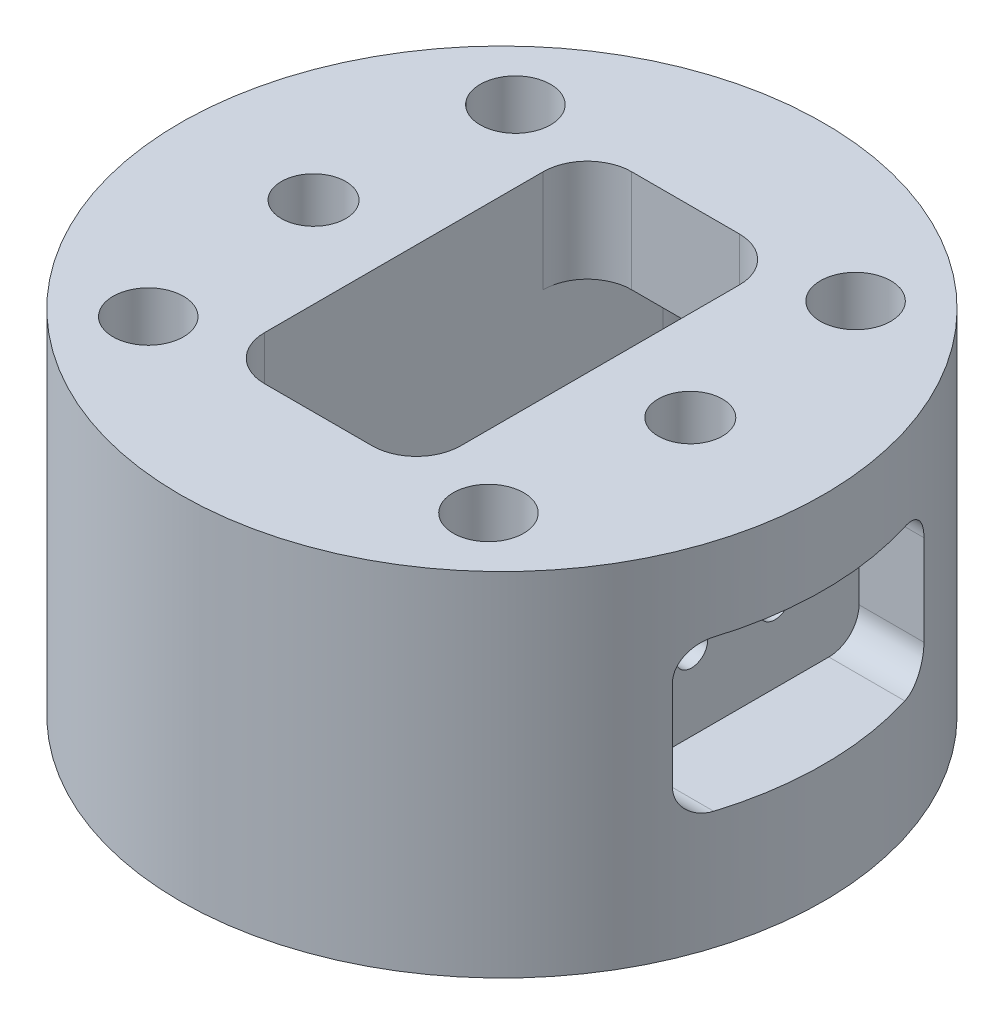
SolidWorks part; units mm, degrees
material "6061 Alloy"
ref_plane "Front Plane" through (0, 0, 0) normal (0, 0, 1) x (1, 0, 0)
ref_plane "Top Plane" through (0, 0, 0) normal (0, 1, 0) x (1, 0, 0)
ref_plane "Right Plane" through (0, 0, 0) normal (1, 0, 0) x (0, 0, -1)
sketch "main_features" plane through (0, 0, 0) normal (0, 1, 0) x (1, 0, 0)
  line L0 (0, 32) -> (0, -32) construction
  line L1 (5.35, 18.25) -> (-5.35, 18.25)
  line L2 (9.75, 13.85) -> (9.75, -13.85)
  line L3 (5.35, -18.25) -> (-5.35, -18.25)
  line L4 (-9.75, 13.85) -> (-9.75, -13.85)
  line L5 (9.75, 18.25) -> (-9.75, -18.25) construction
  line L6 (9.75, -18.25) -> (-9.75, 18.25) construction
  line L7 (-32, 0) -> (32, 0) construction
  line L9 (-7.25, 28.25) -> (7.25, 28.25)
  line L10 (-9.75, 25.75) -> (-9.75, -25.75)
  line L11 (-7.25, -28.25) -> (7.25, -28.25)
  line L12 (9.75, 25.75) -> (9.75, -25.75)
  line L13 (-9.75, 28.25) -> (9.75, -28.25) construction
  line L14 (-9.75, -28.25) -> (9.75, 28.25) construction
  circle A0 centre (0, 0) radius 32
  circle A1 centre (0, -23.5) radius 2 construction
  circle A2 centre (0, 23.5) radius 2 construction
  circle A3 centre (16.9119, 18.25) radius 6.325 construction
  circle A4 centre (16.9119, -18.25) radius 6.325 construction
  circle A5 centre (-16.9119, -18.25) radius 6.325 construction
  circle A6 centre (-16.9119, 18.25) radius 6.325 construction
  circle A7 centre (-6.7, -21.8) radius 0.85 construction
  arc A8 (-5.35, -18.25) -> (-9.75, -13.85) centre (-5.35, -13.85) cw
  arc A9 (9.75, -13.85) -> (5.35, -18.25) centre (5.35, -13.85) cw
  arc A10 (5.35, 18.25) -> (9.75, 13.85) centre (5.35, 13.85) cw
  arc A11 (-5.35, 18.25) -> (-9.75, 13.85) centre (-5.35, 13.85) ccw
  arc A12 (-9.75, -25.75) -> (-7.25, -28.25) centre (-7.25, -25.75) ccw
  arc A13 (7.25, -28.25) -> (9.75, -25.75) centre (7.25, -25.75) ccw
  arc A14 (7.25, 28.25) -> (9.75, 25.75) centre (7.25, 25.75) cw
  arc A15 (-7.25, 28.25) -> (-9.75, 25.75) centre (-7.25, 25.75) ccw
  circle A16 centre (-18.7291, 0) radius 3.2004
  circle A17 centre (18.7291, 0) radius 3.2004
  point P55 (0, 0)
  dimension "D3" = 47
  dimension "D4" = 12.65
  dimension "D7" = 4.4
  dimension "D8" = 64
  dimension "D10" = 2.5
  dimension "D11" = 4
  dimension "D12" = 1.7
  dimension "D13" = 6.4008
  dimension "D1" = 19.5
  dimension "D2" = 36.5
  dimension "D5" = 6.7
  dimension "D6" = 1.7
  dimension "D9" = 56.5
extrude "body" add sketch "main_features" along normal blind 35 contours A0 A15 L9 A14 L12 L2 A13 L11 A12 L10 L4 | L9 A15 L10 A11 L1 A10 L12 A14 | L11 A13 L12 A9 L3 A8 L10 A12 | A16 | A17 region at (0, 0, -22.9428) region at (0, 0, 22.9428) region at (-31.0949, 0, 0) region at (-18.7291, 0, 0) region at (18.7291, 0, 0)
extrude "electrical_cutout" cut sketch "Sketch1<3>" along normal offset from surface (24.84 mm away) 10.16 contours L9 A15 L10 A11 L1 A10 L12 A14 | L11 A13 L12 A9 L3 A8 L10 A12 region at (0, 0, -22.9428) region at (0, 0, 22.9428) up to face at (0, 35, 0)
sketch "Sketch1<3>" plane through (0, 0, 0) normal (0, 1, 0) x (1, 0, 0) same geometry as "main_features"
hole_wizard "electrical_alignment_hole" positions "Sketch6" profile "Sketch7" hole size "Ø1.7" standard "ANSI Metric"
sketch "Sketch6" plane through (0, 24.84, 0) normal (0, 1, 0) x (1, 0, 0)
  point P0 (-6.7, -21.8)
sketch "Sketch7" plane through (-6.7, 24.84, 21.8) normal (1, 0, 0) x (0, 0, -1)
  line L0 (0, 0) -> (0, 5.5107)
  line L1 (0, 5.5107) -> (0.85, 5)
  line L2 (0.85, 5) -> (0.85, 0.025)
  line L3 (0.85, 0.025) -> (0.875, 0)
  line L5 (0.875, 0) -> (0, 0)
  line L6 (-0.85, 0.025) -> (-0.875, 0) construction
  line L10 (0, 5.5107) -> (-0.85, 5) construction
  line L11 (0, -6.35) -> (0, 107.95) construction
  dimension "Hole Dia." = 1.7
  dimension "Hole Depth" = 5
  dimension "Near C'Sink Dia." = 1.75
  dimension "Near C'Sink Angle" = 90
  dimension "Drill Angle" = 118
hole_wizard "electrical_mounting_holes" positions "Sketch8" profile "Sketch9" tap size "M6x1.0" standard "ANSI Metric"
sketch "Sketch8" plane through (0, 24.84, 0) normal (0, 1, 0) x (1, 0, 0)
  point P0 (0, -23.5)
  point P3 (0, 23.5)
sketch "Sketch9" plane through (0, 24.84, 23.5) normal (1, 0, 0) x (0, 0, -1)
  line L0 (0, 0) -> (0, 9.5022)
  line L1 (0, 9.5022) -> (2.5, 8)
  line L2 (2.5, 8) -> (2.5, 0.525)
  line L3 (2.5, 0.525) -> (3.025, 0)
  line L5 (3.025, 0) -> (0, 0)
  line L6 (-2.5, 0.525) -> (-3.025, 0) construction
  line L10 (0, 9.5022) -> (-2.5, 8) construction
  line L11 (0, -6.35) -> (0, 107.95) construction
  dimension "Tap Drill Dia." = 5
  dimension "Tap Drill Depth" = 8
  dimension "Near C'Sink Dia." = 6.05
  dimension "Near C'Sink Angle" = 90
  dimension "Drill Angle" = 118
cosmetic thread "Hole Thread5" parameters "D1"=7, "D2"=6
cosmetic thread "Hole Thread6" parameters "D1"=7, "D2"=6
ref_plane "Plane1" through (0, 0, 18.25) normal (0, 0, 1) x (1, 0, 0)
sketch "push_connector" plane through (0, 0, 18.25) normal (0, 0, 1) x (1, 0, 0)
  line L0 (16.9119, 0) -> (16.9119, 35)
  line L1 (32, 35) -> (-32, 35) construction
  line L2 (23.2369, 0) -> (10.5869, 0) construction
  line L3 (11.6119, 8) -> (22.2119, 8)
  line L4 (11.6119, 8) -> (11.6119, 0)
  line L5 (11.6119, 0) -> (22.2119, 0)
  line L6 (22.2119, 8) -> (22.2119, 0)
  line L7 (11.6119, 8) -> (22.2119, 0) construction
  line L8 (11.6119, 0) -> (22.2119, 8) construction
  line L10 (13.6869, 12.5) -> (20.1369, 12.5)
  line L11 (13.6869, 12.5) -> (13.6869, 0)
  line L12 (13.6869, 0) -> (20.1369, 0)
  line L13 (20.1369, 12.5) -> (20.1369, 0)
  line L14 (13.6869, 12.5) -> (20.1369, 0) construction
  line L15 (13.6869, 0) -> (20.1369, 12.5) construction
  line L16 (12.2369, 10.15) -> (21.5869, 10.15)
  line L17 (12.2369, 10.15) -> (12.2369, 0)
  line L18 (12.2369, 0) -> (21.5869, 0)
  line L19 (21.5869, 10.15) -> (21.5869, 0)
  line L20 (12.2369, 10.15) -> (21.5869, 0) construction
  line L21 (12.2369, 0) -> (21.5869, 10.15) construction
  line L23 (20.4119, 18.23) -> (13.4119, 18.23)
  line L24 (20.4119, 18.23) -> (20.4119, 35)
  line L25 (20.4119, 35) -> (13.4119, 35)
  line L26 (13.4119, 18.23) -> (13.4119, 35)
  line L27 (20.4119, 18.23) -> (13.4119, 35) construction
  line L28 (20.4119, 35) -> (13.4119, 18.23) construction
  line L29 (19.5119, 12.7626) -> (14.3119, 12.7626)
  line L30 (19.5119, 12.7626) -> (19.5119, 18.23)
  line L31 (19.5119, 18.23) -> (14.3119, 18.23)
  line L32 (14.3119, 12.7626) -> (14.3119, 18.23)
  line L33 (19.5119, 12.7626) -> (14.3119, 18.23) construction
  line L34 (19.5119, 18.23) -> (14.3119, 12.7626) construction
  point P5 (16.9119, 4)
  point P12 (16.9119, 6.25)
  point P17 (16.9119, 5.075)
  point P23 (16.9119, 26.615)
  point P28 (16.9119, 15.4963)
  dimension "D1" = 10.6
  dimension "D2" = 9.35
  dimension "D3" = 10.15
  dimension "D4" = 6.45
  dimension "D5" = 12.5
  dimension "D6" = 8
  dimension "D7" = 7
  dimension "D8" = 5.2
  dimension "D9" = 16.77
revolve "push_connector_cutout" cut sketch "push_connector" angle 360 about L0 region at (15.2994, 4, 18.25) region at (15.6119, 15.4963, 18.25) region at (15.2994, 9.075, 18.25) region at (12.9619, 4, 18.25) region at (15.2994, 11.325, 18.25) region at (12.9619, 9.075, 18.25) region at (11.9244, 4, 18.25) region at (15.1619, 26.615, 18.25)
mirror "Mirror1" about plane through (0, 0, 0) normal (1, 0, 0) of "push_connector_cutout"
mirror "Mirror2" about plane through (0, 0, 0) normal (0, 0, 1) of "Mirror1"
extrude "latch_pin_holes" cut sketch "main_features<6>" against normal blind 25 from surface contours A16 | A17 region at (-18.7291, 0, 0) region at (18.7291, 0, 0) starting at face at (16.9119, 35, -14.75)
sketch "main_features<6>" plane through (0, 0, 0) normal (0, 1, 0) x (1, 0, 0) same geometry as "main_features"
ref_plane "Plane2" through (32, 0, 0) normal (1, 0, 0) x (0, 0, -1)
sketch "latch_mechanism_sketch" plane through (32, 0, 0) normal (1, 0, 0) x (0, 0, -1)
  line L0 (0, 35) -> (0, 0) construction
  line L1 (32, 35) -> (-32, 35) construction
  line L2 (25.75, 0) -> (-25.75, 0) construction
  line L3 (-4.1529, 19.267) -> (4.1529, 19.267) construction
  line L5 (9.5, 26.767) -> (-9.5, 26.767)
  line L6 (12.5, 23.767) -> (12.5, 14.767)
  line L7 (9.5, 11.767) -> (-9.5, 11.767)
  line L8 (-12.5, 23.767) -> (-12.5, 14.767)
  line L9 (12.5, 26.767) -> (-12.5, 11.767) construction
  line L10 (12.5, 11.767) -> (-12.5, 26.767) construction
  circle A0 centre (-4.1529, 19.267) radius 1.6129
  circle A1 centre (4.1529, 19.267) radius 1.6129
  arc A2 (9.5, 26.767) -> (12.5, 23.767) centre (9.5, 23.767) cw
  arc A3 (12.5, 14.767) -> (9.5, 11.767) centre (9.5, 14.767) cw
  arc A4 (-9.5, 11.767) -> (-12.5, 14.767) centre (-9.5, 14.767) cw
  arc A5 (-9.5, 26.767) -> (-12.5, 23.767) centre (-9.5, 23.767) ccw
  point P10 (0, 19.267)
  dimension "D1" = 3.2258
  dimension "D2" = 5.08
  dimension "D3" = 3
  dimension "D4" = 15
  dimension "D5" = 25
extrude "release_button_hole" cut sketch "latch_mechanism_sketch<5>" against normal blind 9 contours L5 A5 L8 A4 L7 A3 L6 A2
sketch "latch_mechanism_sketch<5>" plane through (32, 0, 0) normal (1, 0, 0) x (0, 0, -1) same geometry as "latch_mechanism_sketch"
extrude "pins_holes" cut sketch "latch_mechanism_sketch" against normal offset from surface (20.25 mm away) 2 contours A1 | A0 region at (32, 19.267, 4.1529) region at (32, 19.267, -4.1529) up to face at (9.75, 21.17, 0)
equation "\"od2\"= 9.35mm"
equation "\"od1\"= 10.6mm"
equation "\"h1\"= 8mm"
equation "\"h2\"= 10.15mm"
equation "\"od3\"= 6.45mm"
equation "\"h\"= 12.5mm"
equation "\"D1@push_connector\" = \"od1\""
equation "\"D2@push_connector\" = \"od2\""
equation "\"D3@push_connector\" = \"h2\""
equation "\"D4@push_connector\" = \"od3\""
equation "\"D5@push_connector\" = \"h\""
equation "\"D6@push_connector\" = \"h1\""
equation "\"schrader_depth\"= 16.77mm"
equation "\"D9@push_connector\"=\"schrader_depth\""
equation "\"latch_pin_narrow\"=9.97399"
